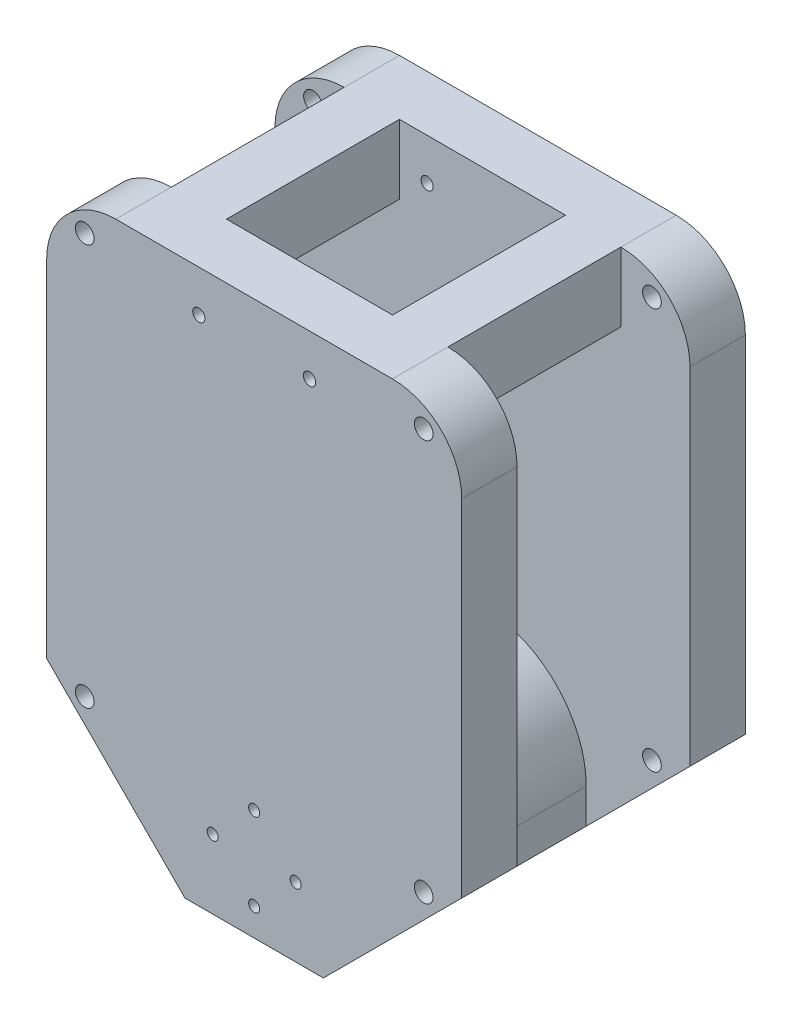
SolidWorks part; units mm, degrees
ref_plane "Front Plane" through (0, 0, 0) normal (0, 0, 1) x (1, 0, 0)
ref_plane "Top Plane" through (0, 0, 0) normal (0, 1, 0) x (1, 0, 0)
ref_plane "Right Plane" through (0, 0, 0) normal (1, 0, 0) x (0, 0, -1)
sketch "Sketch1" plane through (0, 0, 0) normal (0, 0, 1) x (1, 0, 0)
  line L11 (-30, 20.2064) -> (0, 20.2064)
  line L12 (0, 20.2064) -> (30, 20.2064)
  line L13 (30, 20.2064) -> (30, -59.7936)
  line L14 (30, -59.7936) -> (-30, -59.7936)
  line L15 (-30, -59.7936) -> (-30, 20.2064)
  circle A0 centre (-8, 14.2064) radius 0.8836
  circle A1 centre (8, 14.2064) radius 0.8966
  circle A2 centre (0, -49.7936) radius 8 construction
  circle A3 centre (0, -49.7936) radius 6 construction
  circle A4 centre (0, -43.7936) radius 0.8
  circle A5 centre (6, -49.7936) radius 0.8
  circle A6 centre (0, -55.7936) radius 0.8
  circle A7 centre (-6, -49.7936) radius 0.8
  circle A8 centre (-24.5, 16.2064) radius 1.35
  circle A9 centre (24.5, 16.2064) radius 1.35
  circle A10 centre (-24.5, -41.7936) radius 1.35
  circle A11 centre (24.5, -41.7936) radius 1.35
  point P25 (0, -49.7936)
  dimension "D7" = 4
  dimension "D10" = 49
  dimension "D1" = 8
  dimension "D2" = 30
  dimension "D3" = 30
  dimension "D4" = 16
  dimension "D5" = 0
  dimension "D6" = 80
  dimension "D8" = 10
  dimension "D9" = 6
  dimension "D11" = 24.5
  dimension "D12" = 58
  dimension "D13" = 4
extrude "Boss-Extrude1" add sketch "Sketch1" along normal blind 8
sketch "Sketch2" plane through (0, 0, 8) normal (0, 0, 1) x (1, 0, 0)
  line L0 (-12, 20.2064) -> (-12, 10.2064)
  line L1 (30, 20.2064) -> (-30, 20.2064) construction
  line L2 (12, 20.2064) -> (12, 10.2064)
  line L3 (12, 20.2064) -> (20, 20.2064)
  line L4 (20, 20.2064) -> (20, 10.2064)
  line L5 (20, 10.2064) -> (12, 10.2064)
  line L6 (-12, 20.2064) -> (-20, 20.2064)
  line L7 (-20, 20.2064) -> (-20, 10.2064)
  line L8 (-20, 10.2064) -> (-12, 10.2064)
  dimension "D1" = 12
  dimension "D2" = 12
  dimension "D3" = 10
  dimension "D4" = 8
  dimension "D5" = 8
extrude "Boss-Extrude3" add sketch "Sketch2" along normal blind 25
extrude "Boss-Extrude4" add sketch "Sketch1<2>" against normal blind 8 from offset 41
sketch "Sketch1<2>" plane through (0, 0, 0) normal (0, 0, 1) x (1, 0, 0) same geometry as "Sketch1"
sketch "Sketch3" plane through (0, 0, 8) normal (0, 0, 1) x (1, 0, 0)
  line L4 (-30, -59.7936) -> (-10, -59.7936) construction
  line L5 (-6, -49.7936) -> (6, -49.7936) construction
  line L6 (-10, -49.7936) -> (-10, -59.7936)
  line L7 (0, -43.7936) -> (0, -55.7936) construction
  line L8 (10, -49.7936) -> (10, -59.7936)
  line L9 (10, -59.7936) -> (30, -59.7936) construction
  line L10 (-10, -59.7936) -> (10, -59.7936)
  arc A1 (10, -49.7936) -> (-10, -49.7936) centre (0, -49.7936) ccw
extrude "Cut-Extrude1" cut sketch "Sketch3" against normal blind 3
extrude "Cut-Extrude2" cut sketch "Sketch3<2>" along normal blind 3 from surface starting at face at (25.85, -41.7936, 33)
sketch "Sketch3<2>" plane through (0, 0, 8) normal (0, 0, 1) x (1, 0, 0) same geometry as "Sketch3"
sketch "Sketch4" plane through (0, 0, 33) normal (0, 0, -1) x (-1, 0, 0)
  line L0 (-15, -49.7936) -> (-15, -59.7936)
  line L1 (15, -49.7936) -> (15, -59.7936)
  line L2 (-10, -49.7936) -> (-10, -59.7936)
  line L3 (15, -59.7936) -> (30, -59.7936)
  line L4 (-15, -59.7936) -> (-10, -59.7936)
  line L5 (10, -49.7936) -> (10, -59.7936)
  line L6 (-15, -59.7936) -> (-10, -59.7936)
  line L7 (10, -59.7936) -> (15, -59.7936)
  line L8 (15, -59.7936) -> (10, -59.7936)
  line L10 (-15, -59.7936) -> (-10, -59.7936)
  line L11 (10, -59.7936) -> (15, -59.7936)
  line L15 (-30, -59.7936) -> (-10, -59.7936)
  line L16 (-10, -59.7936) -> (-10, -49.7936)
  line L17 (10, -49.7936) -> (10, -59.7936)
  line L18 (10, -59.7936) -> (30, -59.7936)
  line L19 (30, -59.7936) -> (30, 20.2064)
  line L20 (30, 20.2064) -> (20, 20.2064)
  line L21 (20, 20.2064) -> (20, 10.2064)
  line L22 (20, 10.2064) -> (12, 10.2064)
  line L23 (12, 10.2064) -> (12, 20.2064)
  line L24 (12, 20.2064) -> (-12, 20.2064)
  line L25 (-12, 20.2064) -> (-12, 10.2064)
  line L26 (-12, 10.2064) -> (-20, 10.2064)
  line L27 (-20, 10.2064) -> (-20, 20.2064)
  line L28 (-20, 20.2064) -> (-30, 20.2064)
  line L29 (-30, 20.2064) -> (-30, -59.7936)
  line L30 (-30, -59.7936) -> (-15, -59.7936)
  line L34 (30, -59.7936) -> (30, 20.2064)
  line L35 (30, 20.2064) -> (20, 20.2064)
  line L36 (20, 20.2064) -> (20, 10.2064)
  line L37 (20, 10.2064) -> (12, 10.2064)
  line L38 (12, 10.2064) -> (12, 20.2064)
  line L39 (12, 20.2064) -> (-12, 20.2064)
  line L40 (-12, 20.2064) -> (-12, 10.2064)
  line L41 (-12, 10.2064) -> (-20, 10.2064)
  line L42 (-20, 10.2064) -> (-20, 20.2064)
  line L43 (-20, 20.2064) -> (-30, 20.2064)
  line L44 (-30, 20.2064) -> (-30, -59.7936)
  arc A0 (15, -49.7936) -> (-15, -49.7936) centre (0, -49.7936) ccw
  arc A1 (10, -49.7936) -> (-10, -49.7936) centre (0, -49.7936) ccw
  arc A2 (10, -49.7936) -> (-10, -49.7936) centre (0, -49.7936) ccw
  arc A3 (10, -49.7936) -> (-10, -49.7936) centre (0, -49.7936) ccw
  arc A4 (-10, -49.7936) -> (9.3304, -53.3913) centre (0, -49.7936) cw
  dimension "D1" = 0
sketch "Sketch5" plane through (0, 0, 33) normal (0, 0, -1) x (-1, 0, 0)
  line L0 (-15, -49.7936) -> (-15, -59.7936)
  line L1 (-15, -59.7936) -> (-10, -59.7936)
  line L2 (-10, -59.7936) -> (-10, -49.7936)
  line L3 (10, -49.7936) -> (10, -59.7936)
  line L4 (10, -59.7936) -> (15, -59.7936)
  line L5 (15, -59.7936) -> (15, -49.7936)
  arc A0 (10, -49.7936) -> (-10, -49.7936) centre (0, -49.7936) ccw
  arc A1 (15, -49.7936) -> (-15, -49.7936) centre (0, -49.7936) ccw
extrude "Boss-Extrude5" add sketch "Sketch5" along normal blind 25
sketch "Sketch7" plane through (0, 0, 41) normal (0, 0, 1) x (1, 0, 0)
  line L1 (30, 20.2064) -> (30, -59.7936) construction
  line L2 (30, -39.7936) -> (30, -59.7936)
  line L6 (-30, -59.7936) -> (-30, 20.2064) construction
  line L7 (-30, -39.7936) -> (-30, -59.7936)
  line L8 (-30, -39.7936) -> (-10, -59.7936)
  line L9 (10, -59.7936) -> (30, -39.7936)
  line L10 (-30, -59.7936) -> (-10, -59.7936)
  line L11 (10, -59.7936) -> (30, -59.7936)
  dimension "D1" = 20
extrude "Cut-Extrude3" cut sketch "Sketch7" against normal blind 41
fillet "Fillet5" radius 10 4 edges at (-30, 20.2064, 37) (-30, 20.2064, 4) (30, 20.2064, 4) (30, 20.2064, 37)
